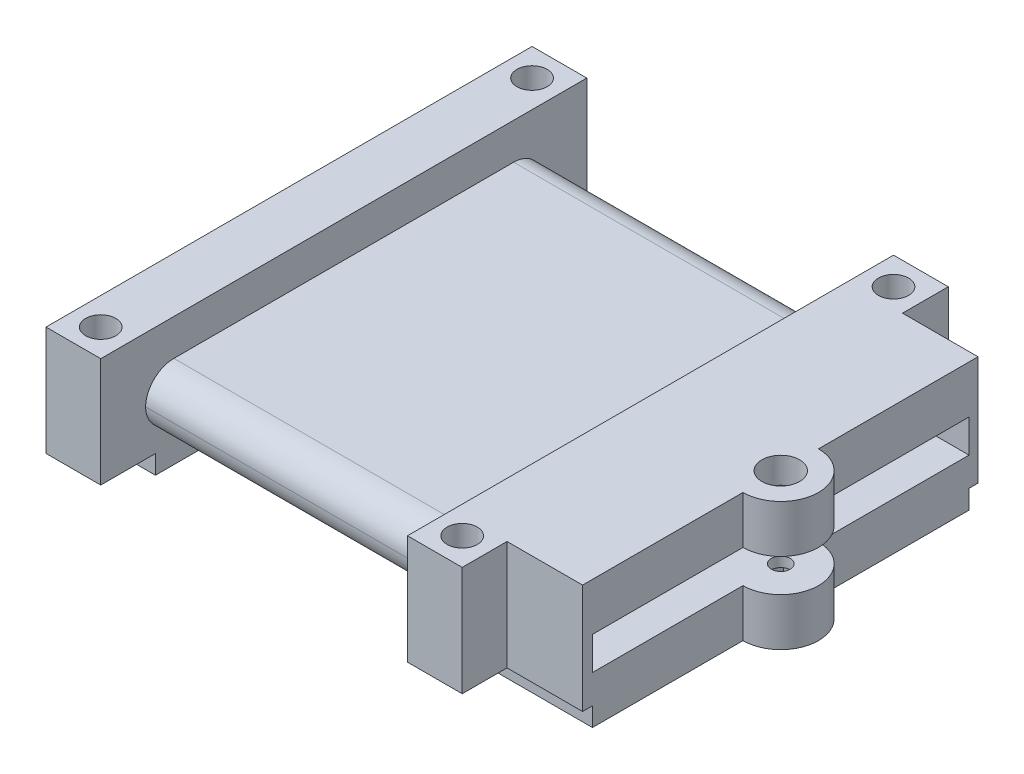
SolidWorks part; units mm, degrees
ref_plane "Front Plane" through (0, 0, 0) normal (0, 0, 1) x (1, 0, 0)
ref_plane "Top Plane" through (0, 0, 0) normal (0, 1, 0) x (1, 0, 0)
ref_plane "Right Plane" through (0, 0, 0) normal (1, 0, 0) x (0, 0, -1)
sketch "Sketch1" plane through (0, 0, 0) normal (1, 0, 0) x (0, 0, -1)
  line L0 (21, 5.9) -> (21, 0) construction
  line L1 (0, 0) -> (42, 0)
  line L2 (0, 0) -> (0, 5.9)
  line L3 (0, 5.9) -> (42, 5.9)
  line L4 (42, 0) -> (42, 5.9)
  line L6 (1.05, 1.2) -> (40.95, 1.2)
  line L7 (1.05, 1.2) -> (1.05, 4.7)
  line L8 (1.05, 4.7) -> (40.95, 4.7)
  line L9 (40.95, 1.2) -> (40.95, 4.7)
  line L10 (1.05, 1.2) -> (40.95, 4.7) construction
  line L11 (1.05, 4.7) -> (40.95, 1.2) construction
  point P7 (21, 2.95)
  dimension "D1" = 42
  dimension "D2" = 5.9
  dimension "D3" = 3.5
  dimension "D4" = 39.9
extrude "Boss-Extrude1" add sketch "Sketch1" along normal blind 32.5
fillet "Fillet2" radius 3 4 edges at (16.25, 0, -42) (16.25, 0, 0) (16.25, 5.9, 0) (16.25, 5.9, -42)
sketch "Sketch2" plane through (32.5, 0, 0) normal (1, 0, 0) x (0, 0, -1)
  line L0 (21, 5.9) -> (21, 0) construction
  line L1 (39, 5.9) -> (3, 5.9) construction
  line L2 (3, 0) -> (39, 0) construction
  line L4 (-4.75, -3.85) -> (46.75, -3.85)
  line L5 (-4.75, -3.85) -> (-4.75, 9.75)
  line L6 (-4.75, 9.75) -> (46.75, 9.75)
  line L7 (46.75, -3.85) -> (46.75, 9.75)
  line L8 (-4.75, -3.85) -> (46.75, 9.75) construction
  line L9 (-4.75, 9.75) -> (46.75, -3.85) construction
  line L14 (40.95, 1.2) -> (1.05, 1.2)
  line L15 (40.95, 1.2) -> (40.95, 4.7)
  line L16 (40.95, 4.7) -> (1.05, 4.7)
  line L17 (1.05, 1.2) -> (1.05, 4.7)
  line L18 (40.95, 1.2) -> (1.05, 4.7) construction
  line L19 (40.95, 4.7) -> (1.05, 1.2) construction
  point P6 (21, 2.95)
  point P11 (21, 2.95)
  point P12 (21, 2.95)
  dimension "D1" = 13.6
  dimension "D2" = 51.5
extrude "Boss-Extrude2" add sketch "Sketch2" along normal blind 5.8
sketch "Sketch3" plane through (0, 0, 0) normal (-1, 0, 0) x (0, 0, 1)
  line L0 (-21, 5.9) -> (-21, 0) construction
  line L1 (-39, 5.9) -> (-3, 5.9) construction
  line L2 (-3, 0) -> (-39, 0) construction
  line L4 (4.75, -3.85) -> (-46.75, -3.85)
  line L5 (4.75, -3.85) -> (4.75, 9.75)
  line L6 (4.75, 9.75) -> (-46.75, 9.75)
  line L7 (-46.75, -3.85) -> (-46.75, 9.75)
  line L8 (4.75, -3.85) -> (-46.75, 9.75) construction
  line L9 (4.75, 9.75) -> (-46.75, -3.85) construction
  line L10 (-1.05, 1.2) -> (-40.95, 1.2)
  line L11 (-1.05, 1.2) -> (-1.05, 4.7)
  line L12 (-1.05, 4.7) -> (-40.95, 4.7)
  line L13 (-40.95, 1.2) -> (-40.95, 4.7)
  line L14 (-1.05, 1.2) -> (-40.95, 4.7) construction
  line L15 (-1.05, 4.7) -> (-40.95, 1.2) construction
  point P6 (-21, 2.95)
  point P12 (-21, 2.95)
extrude "Boss-Extrude3" add sketch "Sketch3" along normal blind 5.8
sketch "Sketch4" plane through (0, 9.75, 0) normal (0, 1, 0) x (1, 0, 0)
  line L0 (-2.9, 46.75) -> (-2.9, 43.85) construction
  line L1 (-5.8, 46.75) -> (0, 46.75) construction
  line L2 (35.4, 46.75) -> (35.4, 43.85) construction
  line L3 (38.3, 46.75) -> (32.5, 46.75) construction
  line L4 (-2.9, -4.75) -> (-2.9, -1.85) construction
  line L5 (-5.8, -4.75) -> (0, -4.75) construction
  line L6 (35.4, -4.75) -> (35.4, -1.85) construction
  line L7 (38.3, -4.75) -> (32.5, -4.75) construction
  circle A0 centre (-2.9, 43.85) radius 1.6
  circle A1 centre (35.4, 43.85) radius 1.6
  circle A2 centre (-2.9, -1.85) radius 1.6
  circle A3 centre (35.4, -1.85) radius 1.6
  dimension "D2" = 3.2
  dimension "D4" = 3.2
  dimension "D6" = 3.2
  dimension "D8" = 3.2
  dimension "D1" = 2.9
  dimension "D3" = 2.9
  dimension "D5" = 2.9
  dimension "D7" = 2.9
extrude "Cut-Extrude1" cut sketch "Sketch4" against normal through all
sketch "Sketch6" plane through (38.3, 0, 0) normal (1, 0, 0) x (0, 0, -1)
  line L0 (46.75, -3.85) -> (46.75, 9.75) construction
  line L1 (-4.75, -3.85) -> (46.75, -3.85)
  line L2 (-4.75, -3.85) -> (-4.75, 3.35)
  line L3 (-4.75, 3.35) -> (46.75, 3.35)
  line L4 (46.75, -3.85) -> (46.75, 3.35)
  dimension "D1" = 7.2
extrude "Cut-Extrude2" [suppressed] cut sketch "Sketch6" against normal blind 5.8
sketch "Sketch7" plane through (-5.8, 0, 0) normal (-1, 0, 0) x (0, 0, 1)
  line L0 (4.75, -3.85) -> (4.75, 9.75) construction
  line L1 (-46.75, -3.85) -> (4.75, -3.85)
  line L2 (-46.75, -3.85) -> (-46.75, 3.35)
  line L3 (-46.75, 3.35) -> (4.75, 3.35)
  line L4 (4.75, -3.85) -> (4.75, 3.35)
  dimension "D1" = 7.2
extrude "Cut-Extrude3" [suppressed] cut sketch "Sketch7" against normal blind 5.8
sketch "Sketch8" plane through (0, 9.75, 0) normal (0, 1, 0) x (1, 0, 0)
  line L1 (46.3, 21) -> (38.3, 21) construction
  line L2 (38.3, 46.75) -> (38.3, -4.75) construction
  line L3 (46.3, 25) -> (46.3, 41.9)
  line L4 (46.3, 41.9) -> (38.3, 41.9)
  line L5 (46.3, 17) -> (46.3, 0)
  line L6 (46.3, 0) -> (38.3, 0)
  circle A0 centre (46.3, 21) radius 4
  line M5 (38.3, -4.75) -> (38.3, 46.75)
  dimension "D1" = 8
  dimension "D2" = 90
  dimension "D3" = 8
  dimension "D4" = 16.9
extrude "Boss-Extrude4" add sketch "Sketch8" against normal blind 13.6 contours L1 A0 L3 L4 M5 | A0 L1 L6 L5 M5 | A0 region at (42.1139, 9.75, -9.7884) region at (42.1129, 9.75, -32.1613) region at (43.5516, 9.75, -23.7484)
hole_wizard "CSK for M2 Flat Head Machine Screw1" positions "Sketch12" profile "Sketch13" countersink size "M2" standard "ANSI Metric" end condition through all
sketch "Sketch12" plane through (0, 9.75, 0) normal (0, 1, 0) x (1, 0, 0)
  point P0 (46.3, 21)
sketch "Sketch13" plane through (46.3, 9.75, -21) normal (1, 0, 0) x (0, 0, 1)
  line L0 (0, 0) -> (0, 13.6)
  line L1 (0, 13.6) -> (1, 13.6)
  line L2 (1, 13.6) -> (1, 3.75)
  line L3 (1, 3.75) -> (2, 2.75)
  line L4 (2, 2.75) -> (2, 0)
  line L6 (2, 0) -> (0, 0)
  line L7 (-1, 3.75) -> (-2, 2.75) construction
  line L11 (0, -6.35) -> (0, 107.95) construction
  dimension "Thru Hole Dia." = 2
  dimension "Thru Hole Depth" = 13.6
  dimension "C'Sink Dia." = 4
  dimension "C'Sink Angle" = 90
  dimension "Head Clearance" = 2.75
sketch "Sketch14" plane through (0, -3.85, 0) normal (0, -1, 0) x (1, 0, 0)
  line L1 (43.9126, -20.5753) -> (44.7385, -22.8552)
  line L2 (44.7385, -22.8552) -> (47.1259, -23.2799)
  line L3 (47.1259, -23.2799) -> (48.6874, -21.4247)
  line L4 (48.6874, -21.4247) -> (47.8615, -19.1448)
  line L5 (47.8615, -19.1448) -> (45.4741, -18.7201)
  line L6 (45.4741, -18.7201) -> (43.9126, -20.5753)
  circle A0 centre (46.3, -21) radius 2.1 construction
  dimension "D1" = 4.2
extrude "Cut-Extrude4" cut sketch "Sketch14" against normal blind 4
sketch "Sketch15" plane through (-5.8, 0, 0) normal (-1, 0, 0) x (0, 0, 1)
  line L1 (-40.95, 1.2) -> (-1.05, 1.2)
  line L2 (-40.95, 1.2) -> (-40.95, 4.7)
  line L3 (-40.95, 4.7) -> (-1.05, 4.7)
  line L4 (-1.05, 1.2) -> (-1.05, 4.7)
  line L5 (-46.75, -3.85) -> (-40.95, -3.85)
  line L6 (-46.75, -3.85) -> (-46.75, -1.85)
  line L7 (-46.75, -1.85) -> (-40.95, -1.85)
  line L8 (-40.95, -3.85) -> (-40.95, -1.85)
  line L9 (4.75, -3.85) -> (-1.05, -3.85)
  line L10 (4.75, -3.85) -> (4.75, -1.85)
  line L11 (4.75, -1.85) -> (-1.05, -1.85)
  line L12 (-1.05, -3.85) -> (-1.05, -1.85)
  dimension "D1" = 5.8
  dimension "D2" = 2
  dimension "D3" = 5.8
  dimension "D4" = 2
extrude "Cut-Extrude5" cut sketch "Sketch15" against normal through all
